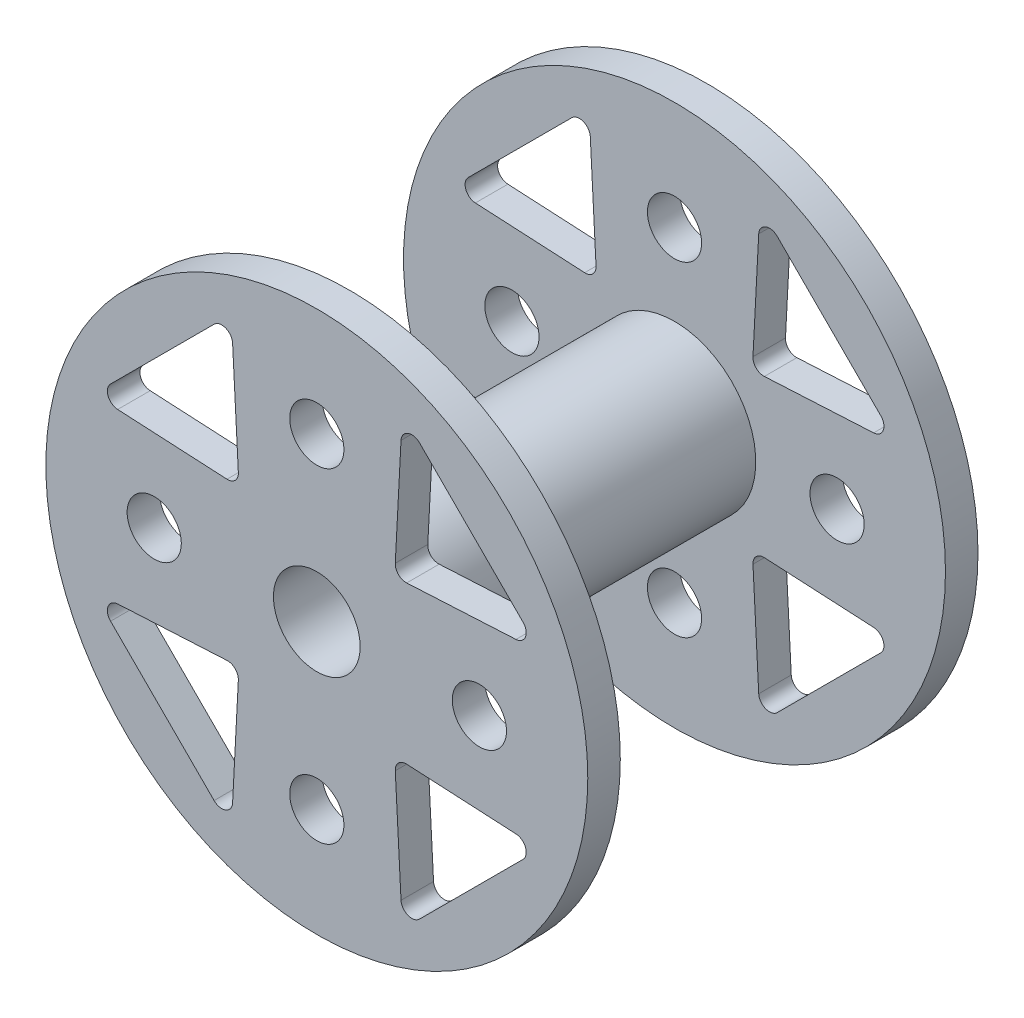
SolidWorks part; units mm, degrees
ref_plane "Alzado" through (0, 0, 0) normal (0, 0, 1) x (1, 0, 0)
ref_plane "Planta" through (0, 0, 0) normal (0, 1, 0) x (1, 0, 0)
ref_plane "Vista lateral" through (0, 0, 0) normal (1, 0, 0) x (0, 0, -1)
sketch "Croquis1" plane through (0, 0, 0) normal (0, 0, 1) x (1, 0, 0)
  circle A0 centre (0, 0) radius 4
  circle A1 centre (0, 0) radius 7.5
  dimension "D1" = 8
  dimension "D2" = 15
extrude "Saliente-Extruir1" add sketch "Croquis1" along normal blind 30
sketch "Croquis2" plane through (0, 0, 30) normal (0, 0, 1) x (1, 0, 0)
  line L0 (0, 0) -> (-17.6777, 17.6777) construction
  line L1 (-15, 0) -> (0, 0) construction
  line L2 (-19.0278, 9.4753) -> (-9.4753, 19.0278)
  line L3 (-18.3733, 7.7696) -> (-8.2901, 7.2389)
  line L4 (-7.2389, 8.2901) -> (-7.7696, 18.3733)
  line L5 (7.7696, 18.3733) -> (7.2389, 8.2901)
  line L6 (9.4753, 19.0278) -> (19.0278, 9.4753)
  line L7 (8.2901, 7.2389) -> (18.3733, 7.7696)
  line L8 (18.3733, -7.7696) -> (8.2901, -7.2389)
  line L9 (19.0278, -9.4753) -> (9.4753, -19.0278)
  line L10 (7.2389, -8.2901) -> (7.7696, -18.3733)
  line L11 (-7.7696, -18.3733) -> (-7.2389, -8.2901)
  line L12 (-9.4753, -19.0278) -> (-19.0278, -9.4753)
  line L13 (-8.2901, -7.2389) -> (-18.3733, -7.7696)
  circle A0 centre (0, 0) radius 25
  circle A1 centre (0, 0) radius 4
  arc A2 (-8.2901, 7.2389) -> (-7.2389, 8.2901) centre (-8.2375, 8.2375) ccw
  circle A3 centre (0, 0) radius 15 construction
  circle A4 centre (0, 0) radius 4 construction
  circle A5 centre (0, 15) radius 2.5
  circle A6 centre (15, 0) radius 2.5
  circle A7 centre (0, -15) radius 2.5
  circle A8 centre (-15, 0) radius 2.5
  arc A9 (-9.4753, 19.0278) -> (-7.7696, 18.3733) centre (-8.7682, 18.3207) cw
  arc A10 (-19.0278, 9.4753) -> (-18.3733, 7.7696) centre (-18.3207, 8.7682) ccw
  arc A11 (9.4753, 19.0278) -> (7.7696, 18.3733) centre (8.7682, 18.3207) ccw
  arc A12 (19.0278, 9.4753) -> (18.3733, 7.7696) centre (18.3207, 8.7682) cw
  arc A13 (7.2389, 8.2901) -> (8.2901, 7.2389) centre (8.2375, 8.2375) ccw
  arc A14 (19.0278, -9.4753) -> (18.3733, -7.7696) centre (18.3207, -8.7682) ccw
  arc A15 (9.4753, -19.0278) -> (7.7696, -18.3733) centre (8.7682, -18.3207) cw
  arc A16 (8.2901, -7.2389) -> (7.2389, -8.2901) centre (8.2375, -8.2375) ccw
  arc A17 (-9.4753, -19.0278) -> (-7.7696, -18.3733) centre (-8.7682, -18.3207) ccw
  arc A18 (-19.0278, -9.4753) -> (-18.3733, -7.7696) centre (-18.3207, -8.7682) cw
  arc A19 (-7.2389, -8.2901) -> (-8.2901, -7.2389) centre (-8.2375, -8.2375) ccw
  point P18 (0, 0)
  point P23 (-7.1805, 7.1805)
  point P26 (-7.8876, 20.6156)
  point P29 (-20.6156, 7.8876)
  point P59 (0, 0)
  dimension "D1" = 50
  dimension "D2" = 30
  dimension "D3" = 5
  dimension "D9" = 1
  dimension "D5" = 45
  dimension "D6" = 9
  dimension "D7" = 9
  dimension "D8" = 10
  dimension "D4" = 4
  dimension "D10" = 4
extrude "Saliente-Extruir2" add sketch "Croquis2" along normal blind 3
ref_plane "Plano1" through (0, 0, 15) normal (0, 0, -1) x (-1, 0, 0)
mirror "Simetría1" about plane through (0, 0, 15) normal (0, 0, -1) of "Saliente-Extruir2"
